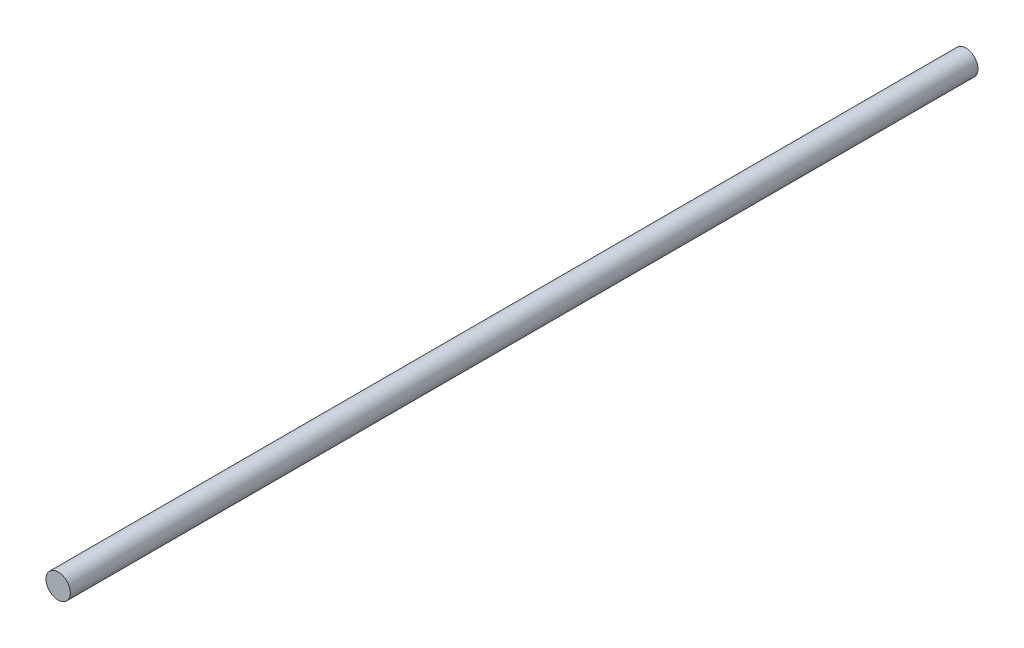
SolidWorks part; units mm, degrees
ref_plane "Front Plane" through (0, 0, 0) normal (0, 0, 1) x (1, 0, 0)
ref_plane "Top Plane" through (0, 0, 0) normal (0, 1, 0) x (1, 0, 0)
ref_plane "Right Plane" through (0, 0, 0) normal (1, 0, 0) x (0, 0, -1)
sketch "Sketch1" plane through (0, 0, 0) normal (0, 0, 1) x (1, 0, 0)
  circle A0 centre (0, 0) radius 5
extrude "Boss-Extrude1" add sketch "Sketch1" along normal blind 373
